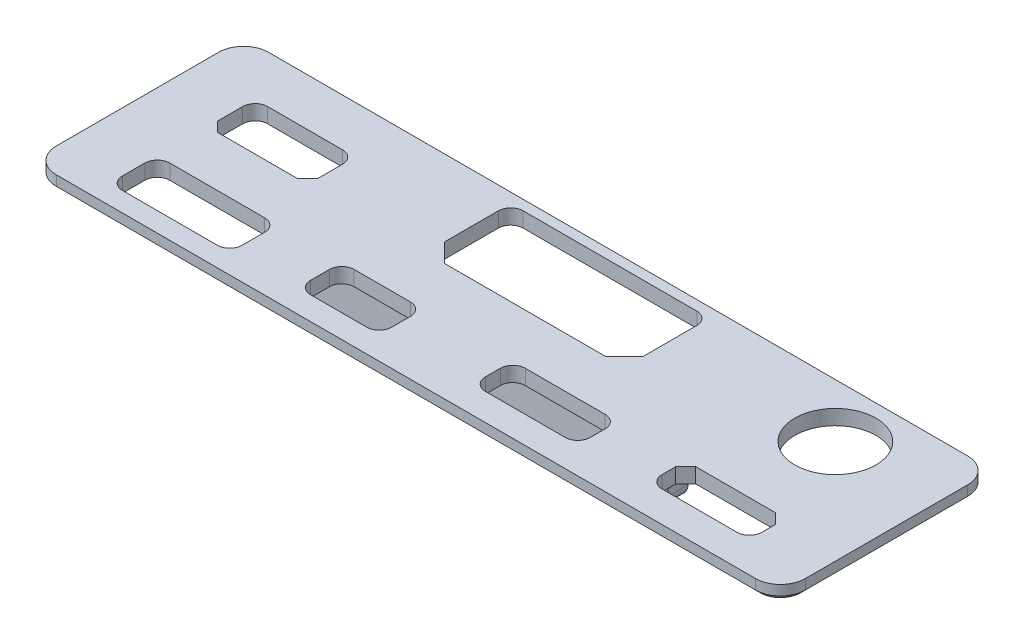
SolidWorks part; units mm, degrees
ref_plane "前视基准面" through (0, 0, 0) normal (0, 0, 1) x (1, 0, 0)
ref_plane "上视基准面" through (0, 0, 0) normal (0, 1, 0) x (1, 0, 0)
ref_plane "右视基准面" through (0, 0, 0) normal (1, 0, 0) x (0, 0, -1)
sketch "草图1" plane through (0, 0, 0) normal (0, 1, 0) x (1, 0, 0)
  line L1 (-30, 8.5) -> (30, 8.5)
  line L2 (-30, 8.5) -> (-30, -8.5)
  line L3 (-30, -8.5) -> (30, -8.5)
  line L4 (30, 8.5) -> (30, -8.5)
  line L5 (-30, 8.5) -> (30, -8.5) construction
  line L6 (-30, -8.5) -> (30, 8.5) construction
  point P0 (0, 0)
  dimension "D1" = 60
  dimension "D2" = 17
extrude "凸台-拉伸1" add sketch "草图1" along normal blind 1.2
sketch "草图4" plane through (0, 1.2, 0) normal (0, 1, 0) x (1, 0, 0)
  line L0 (-30, 8.5) -> (-30, -8.5) construction
  line L1 (-25.2717, 4.7) -> (-17.2717, 4.7)
  line L2 (-25.2717, 4.7) -> (-25.2717, 0.9)
  line L3 (-25.2717, 0.9) -> (-17.2717, 0.9)
  line L4 (-17.2717, 4.7) -> (-17.2717, 0.9)
  line L5 (-7.8, 7.7) -> (8.1, 7.7)
  line L6 (-7.8, 7.7) -> (-7.8, 0.9)
  line L7 (-7.8, 0.9) -> (8.1, 0.9)
  line L8 (8.1, 7.7) -> (8.1, 0.9)
  line L13 (17.05, -3.1348) -> (25.05, -3.1348)
  line L14 (17.05, -3.1348) -> (17.05, -6.0348)
  line L15 (17.05, -6.0348) -> (25.05, -6.0348)
  line L16 (25.05, -3.1348) -> (25.05, -6.0348)
  line L17 (3.2, -3.1348) -> (11.6, -3.1348)
  line L18 (3.2, -3.1348) -> (3.2, -6.3348)
  line L19 (3.2, -6.3348) -> (11.6, -6.3348)
  line L20 (11.6, -3.1348) -> (11.6, -6.3348)
  line L21 (-10.5, -3.1348) -> (-4, -3.1348)
  line L22 (-10.5, -3.1348) -> (-10.5, -6.6348)
  line L23 (-10.5, -6.6348) -> (-4, -6.6348)
  line L24 (-4, -3.1348) -> (-4, -6.6348)
  line L25 (-25.2717, -3.1348) -> (-15.6717, -3.1348)
  line L26 (-25.2717, -3.1348) -> (-25.2717, -6.9348)
  line L27 (-25.2717, -6.9348) -> (-15.6717, -6.9348)
  line L28 (-15.6717, -3.1348) -> (-15.6717, -6.9348)
  line L29 (30, 8.5) -> (-30, 8.5) construction
  line L31 (30, -8.5) -> (30, 8.5) construction
  line L32 (30, 8.5) -> (-30, 8.5) construction
  circle A0 centre (21.7, 4.2) radius 3.25
  dimension "D21" = 6.5
  dimension "D1" = 3.5
  dimension "D2" = 6.5
  dimension "D3" = 8.4
  dimension "D4" = 3.2
  dimension "D5" = 8
  dimension "D6" = 3.8
  dimension "D7" = 15.9
  dimension "D8" = 8
  dimension "D9" = 2.9
  dimension "D10" = 4.7283
  dimension "D11" = 7.6
  dimension "D12" = 11.6348
  dimension "D13" = 19.5
  dimension "D14" = 33.2
  dimension "D15" = 4.95
  dimension "D17" = 22.2
  dimension "D19" = 8.3
  dimension "D20" = 4.3
  dimension "D22" = 6.8
  dimension "D23" = 9.6
extrude "切除-拉伸1" cut sketch "草图4" against normal up to next
fillet "圆角2" radius 1 18 edges at (-25.2717, 0.6, -4.7) (-17.2717, 0.6, -4.7) (8.1, 0.6, -7.7) (-7.8, 0.6, -7.7) (25.05, 0.6, 6.0348) (17.05, 0.6, 6.0348) (11.6, 0.6, 6.3348) (11.6, 0.6, 3.1348) (3.2, 0.6, 3.1348) (3.2, 0.6, 6.3348) (-4, 0.6, 6.6348) (-4, 0.6, 3.1348) (-10.5, 0.6, 3.1348) (-10.5, 0.6, 6.6348) (-15.6717, 0.6, 6.9348) (-15.6717, 0.6, 3.1348) (-25.2717, 0.6, 3.1348) (-25.2717, 0.6, 6.9348)
chamfer "倒角1" distance 0.8 angle 45 4 edges at (17.05, 0.6, 3.1348) (25.05, 0.6, 3.1348) (-17.2717, 0.6, -0.9) (-25.2717, 0.6, -0.9)
sketch "草图5" plane through (0, 0, 0) normal (0, -1, 0) x (1, 0, 0)
  line L0 (-30, -8.5) -> (-30, 8.5) construction
  line L1 (-13.9089, -3.3832) -> (-12.4089, -3.3832)
  line L2 (-13.9089, -3.3832) -> (-13.9089, 4.6168)
  line L3 (-13.9089, 4.6168) -> (-12.4089, 4.6168)
  line L4 (-12.4089, -3.3832) -> (-12.4089, 4.6168)
  line L5 (13.0911, -3.3832) -> (14.5911, -3.3832)
  line L6 (13.0911, -3.3832) -> (13.0911, 4.6168)
  line L7 (13.0911, 4.6168) -> (14.5911, 4.6168)
  line L8 (14.5911, -3.3832) -> (14.5911, 4.6168)
  line L9 (30, -8.5) -> (-30, -8.5) construction
  line L10 (30, 8.5) -> (30, -8.5) construction
  dimension "D1" = 1.5
  dimension "D2" = 8
  dimension "D3" = 1.5
  dimension "D4" = 8
  dimension "D5" = 16.0911
  dimension "D6" = 5.1168
  dimension "D7" = 5.1168
  dimension "D8" = 15.4089
extrude "凸台-拉伸2" add sketch "草图5" along normal blind 1.2
sketch "草图6" plane through (0, 0, 0) normal (0, -1, 0) x (1, 0, 0)
  line L0 (-13.9089, 4.6168) -> (-13.9089, -3.3832) construction
  line L1 (-13.9089, 2.1) -> (14.5911, 2.1)
  line L2 (-13.9089, 2.1) -> (-13.9089, 0.5)
  line L3 (-13.9089, 0.5) -> (14.5911, 0.5)
  line L4 (14.5911, 2.1) -> (14.5911, 0.5)
  line L5 (30, -8.5) -> (-30, -8.5) construction
  dimension "D1" = 1.6
  dimension "D2" = 9
extrude "凸台-拉伸3" add sketch "草图6" along normal blind 4
fillet "圆角3" radius 1 2 edges at (14.5911, -4, 1.3) (-13.9089, -4, 1.3)
chamfer "倒角2" distance 1 angle 45 4 edges at (13.8411, -1.2, -3.3832) (-13.1589, -1.2, -3.3832) (13.8411, -1.2, 4.6168) (-13.1589, -1.2, 4.6168)
fillet "圆角4" radius 2 4 edges at (30, 0.6, 8.5) (30, 0.6, -8.5) (-30, 0.6, 8.5) (-30, 0.6, -8.5)
chamfer "倒角5" distance 0.4 angle 45 8 edges at (0, 0, -8.5) (-29.4142, 0, -7.9142) (29.4142, 0, -7.9142) (-30, 0, 0) (30, 0, 0) (-29.4142, 0, 7.9142) (29.4142, 0, 7.9142) (0, 0, 8.5)
chamfer "倒角6" distance 1.5 angle 45 2 edges at (8.1, 0.6, -0.9) (-7.8, 0.6, -0.9)
